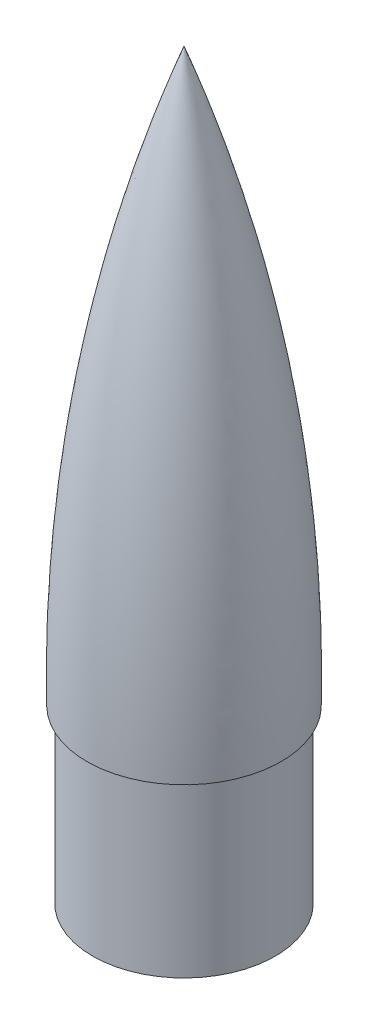
SolidWorks part; units mm, degrees
ref_plane "Спереди" through (0, 0, 0) normal (0, 0, 1) x (1, 0, 0)
ref_plane "Сверху" through (0, 0, 0) normal (0, 1, 0) x (1, 0, 0)
ref_plane "Справа" through (0, 0, 0) normal (1, 0, 0) x (0, 0, -1)
sketch "Эскиз1" plane through (0, 0, 0) normal (0, 1, 0) x (1, 0, 0)
  circle A0 centre (0, 0) radius 15
  circle A1 centre (0, 0) radius 16
  dimension "D1" = 32
  dimension "D2" = 30
extrude "Бобышка-Вытянуть1" add sketch "Эскиз1" along normal blind 30
sketch "Эскиз5" plane through (0, 0, 0) normal (0, 0, 1) x (1, 0, 0)
  line L0 (0, 100) -> (0, 0) construction
  line L1 (0, 30) -> (0, 130)
  line L2 (0, 30) -> (-17, 30)
  line L3 (16, 30) -> (-16, 30) construction
  arc A1 (0, 130) -> (-17, 30) centre (257.5302, 34.7749) ccw
revolve "Повернуть1" add sketch "Эскиз5" angle 360 about L0
sketch "Эскиз6" plane through (0, 0, 0) normal (0, 0, 1) x (1, 0, 0)
  line L2 (0, 127.5) -> (-1.2853, 123.6776) construction
  line L3 (-1.2853, 123.6776) -> (-2.1438, 120.7719) construction
  line L9 (-2.1438, 120.7719) -> (-5.6376, 103.8091) construction
  line L20 (0, 30) -> (0, 130) construction
  line L21 (0, 127.5) -> (0, 30)
  line L22 (-2.5, 32.5) -> (-2.5, 114.8206)
  line L23 (-14.532, 32.5) -> (-2.5, 32.5)
  line L26 (0, 30) -> (-15, 30)
  line L27 (0, 30) -> (-17, 30) construction
  line L28 (-14.4536, 41.6899) -> (-14.5645, 36.7098) construction
  line L29 (-14.5645, 36.7098) -> (-15, 30) construction
  arc A5 (-2.5, 114.8206) -> (-14.532, 32.5) centre (257.5302, 34.7749) ccw
  arc A6 (-5.6376, 103.8091) -> (-14.4536, 41.6899) centre (257.5302, 34.7749) ccw
  spline S0 degree 2 poles (-14.4536, 41.6899) (-14.5645, 36.7098) (-15, 30) knots 0 0 0 1 1 1
  spline S1 degree 3 poles (0, 127.5) (-1.2853, 123.6776) (-2.1438, 120.7719) (-5.6376, 103.8091) knots 0 0 0 0 1 1 1 1
  point P0 (0, 127.5)
  dimension "D2" = 2.5
  dimension "D3" = 2
  dimension "D1" = 2.5
revolve "Вырез-Повернуть1" cut sketch "Эскиз6" angle 360 about L21
sketch "Эскиз7" plane through (0, 0, 0) normal (0, 0, 1) x (1, 0, 0)
  line L0 (-16, 0) -> (16, 0) construction
  circle A0 centre (0, 2.5) radius 0.8
  point P0 (0, 0)
  dimension "D1" = 1.6
  dimension "D2" = 2.5
extrude "Вырез-Вытянуть1" cut sketch "Эскиз7" against normal through all
